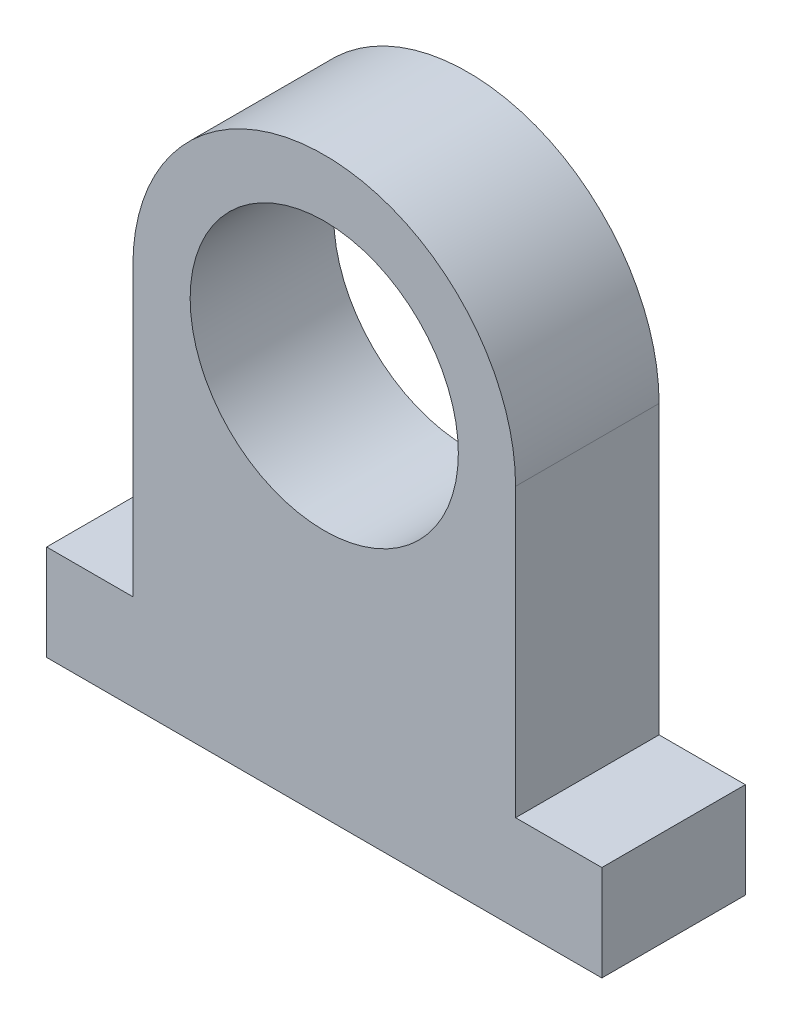
SolidWorks part; units mm, degrees
ref_plane "Front Plane" through (0, 0, 0) normal (0, 0, 1) x (1, 0, 0)
ref_plane "Top Plane" through (0, 0, 0) normal (0, 1, 0) x (1, 0, 0)
ref_plane "Right Plane" through (0, 0, 0) normal (1, 0, 0) x (0, 0, -1)
sketch "Sketch1" plane through (0, 19.05, 0) normal (0, 1, 0) x (1, 0, 0)
  line L0 (17.8, -59.4106) -> (-17.8, -59.4106) construction
  line L1 (-36.85, -78.4606) -> (36.85, -78.4606)
  line L2 (-36.85, -78.4606) -> (-36.85, -97.5106)
  line L3 (-36.85, -97.5106) -> (36.85, -97.5106)
  line L4 (36.85, -78.4606) -> (36.85, -97.5106)
  line L5 (-17.8, -113.4106) -> (17.8, -113.4106) construction
  line L6 (-17.8, -113.4106) -> (17.8, -113.4106) construction
  dimension "D1" = 19.05
  dimension "D2" = 19.05
  dimension "D3" = 19.05
  dimension "D4" = 19.05
extrude "Boss-Extrude2" add sketch "Sketch1" along normal blind 76.2
sketch "Sketch2" plane through (0, 0, 97.5106) normal (0, 0, 1) x (1, 0, 0)
  line L0 (-36.85, 95.25) -> (36.85, 95.25) construction
  line L1 (-36.85, 31.75) -> (36.85, 31.75)
  line L4 (0, 95.25) -> (0, 69.85) construction
  line L5 (-25.4, 69.85) -> (-25.4, 31.75)
  line L6 (25.4, 69.85) -> (25.4, 31.75)
  line L8 (-36.85, 19.05) -> (36.85, 19.05)
  line L9 (36.85, 19.05) -> (36.85, 95.25)
  line L10 (36.85, 95.25) -> (-36.85, 95.25)
  line L11 (-36.85, 95.25) -> (-36.85, 19.05)
  line L12 (-36.85, 19.05) -> (36.85, 19.05)
  line L13 (36.85, 19.05) -> (36.85, 95.25)
  line L14 (36.85, 95.25) -> (-36.85, 95.25)
  line L15 (-36.85, 95.25) -> (-36.85, 19.05)
  circle A0 centre (0, 69.85) radius 17.8 construction
  circle A1 centre (0, 69.85) radius 17.8
  circle A2 centre (0, 69.85) radius 25.4
  line M8 (36.85, 19.05) -> (36.85, 95.25)
  line M9 (36.85, 95.25) -> (-36.85, 95.25)
  line M10 (-36.85, 95.25) -> (-36.85, 19.05)
  dimension "D2" = 12.7
  dimension "D1" = 0
extrude "Cut-Extrude1" cut sketch "Sketch2" against normal through all contours A2 L14 L1 L5 M10 | A2 L6 L1 M8 M9 | A1 region at (-29.3017, 67.6713, 97.5106) region at (29.3017, 67.6713, 97.5106)
